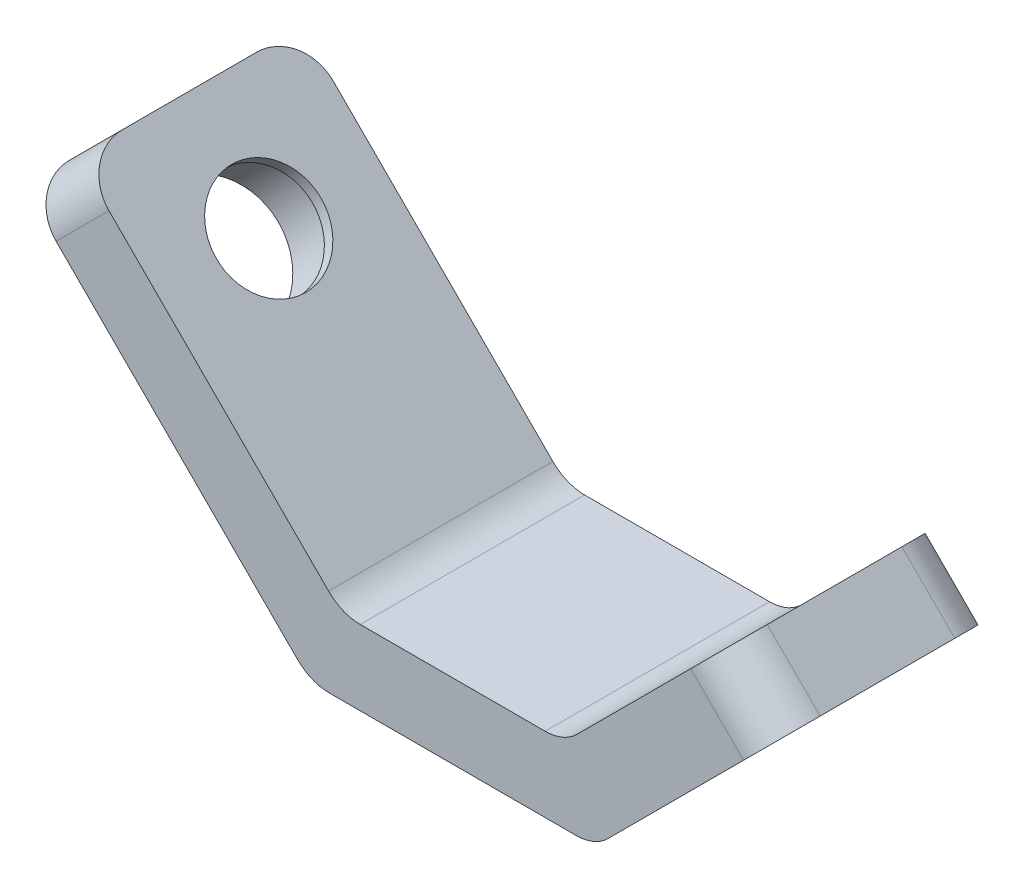
SolidWorks part; units mm, degrees
ref_plane "正面" through (0, 0, 0) normal (0, 0, 1) x (1, 0, 0)
ref_plane "平面" through (0, 0, 0) normal (0, 1, 0) x (1, 0, 0)
ref_plane "右側面" through (0, 0, 0) normal (1, 0, 0) x (0, 0, -1)
sketch "ｽｹｯﾁ1" plane through (0, 0, 0) normal (0, 0, 1) x (1, 0, 0)
  line L0 (0, 0) -> (-19.1421, 19.1421)
  line L1 (-19.1421, 19.1421) -> (-15.6066, 22.6777)
  line L2 (-15.6066, 22.6777) -> (2.0711, 5)
  line L3 (2.0711, 5) -> (16.9203, 5)
  line L4 (16.9203, 5) -> (27.5269, 15.6066)
  line L5 (27.5269, 15.6066) -> (31.0624, 12.0711)
  line L6 (31.0624, 12.0711) -> (18.9914, 0)
  line L7 (18.9914, 0) -> (0, 0)
  point P6 (-10.3033, 17.3744)
  point P10 (22.2236, 10.3033)
  dimension "D1" = 135
  dimension "D2" = 135
  dimension "D3" = 5
  dimension "D4" = 5
  dimension "D5" = 5
  dimension "D6" = 25
  dimension "D7" = 15
  dimension "D8" = 7.5
  dimension "D9" = 7.5
  dimension "D10" = 18
extrude "ﾎﾞｽ - 押し出し1" add sketch "ｽｹｯﾁ1" along normal mid plane 15
sketch "ｽｹｯﾁ2" plane through (3.5355, 3.5355, 0) normal (-0.7071, -0.7071, 0) x (0, 0, 1)
  line L1 (7.5, 27.0711) -> (-7.5, 27.0711) construction
  circle A0 centre (0, 19.5711) radius 4.2
  dimension "D1" = 8.4
  dimension "D2" = 7.5
extrude "ｶｯﾄ - 押し出し1" cut sketch "ｽｹｯﾁ2" against normal through all both and the other way through all
sketch "ｽｹｯﾁ3" plane through (9.4957, -9.4957, 0) normal (0.7071, -0.7071, 0) x (0, 0, -1)
  line L1 (-7.5, 30.5) -> (7.5, 30.5) construction
  circle A0 centre (0, 23) radius 4.2
  point P7 (0, 30.5)
  dimension "D1" = 8.4
  dimension "D2" = 7.5
extrude "ｶｯﾄ - 押し出し2" cut sketch "ｽｹｯﾁ3" against normal through all both and the other way through all
fillet "ﾌｨﾚｯﾄ1" radius 3 8 edges at (29.2947, 13.8388, -7.5) (29.2947, 13.8388, 7.5) (-17.3744, 20.9099, -7.5) (-17.3744, 20.9099, 7.5) (18.9914, 0, 0) (0, 0, 0) (16.9203, 5, 0) (2.0711, 5, 0)
sketch "ｽｹｯﾁ4" plane through (3.5355, 3.5355, 0) normal (-0.7071, -0.7071, 0) x (0, 0, 1)
  circle A0 centre (0, 19.5711) radius 4.2
  circle A1 centre (0, 19.5711) radius 3.5
  circle A2 centre (0, 19.5711) radius 4.2 construction
  dimension "D1" = 7
extrude "ﾎﾞｽ - 押し出し2" add sketch "ｽｹｯﾁ4" along normal blind 0.8
sketch "ｽｹｯﾁ5" plane through (9.4957, -9.4957, 0) normal (-0.7071, 0.7071, 0) x (0, 0, 1)
  circle A0 centre (0, 23) radius 4.2 construction
  circle A1 centre (0, 23) radius 4.2
  circle A2 centre (0, 23) radius 3.5
  dimension "D1" = 7
extrude "ﾎﾞｽ - 押し出し3" add sketch "ｽｹｯﾁ5" along normal blind 0.8
equation "\"D4@ｽｹｯﾁ1\"=\"D3@ｽｹｯﾁ1\""
equation "\"D5@ｽｹｯﾁ1\"=\"D3@ｽｹｯﾁ1\""
